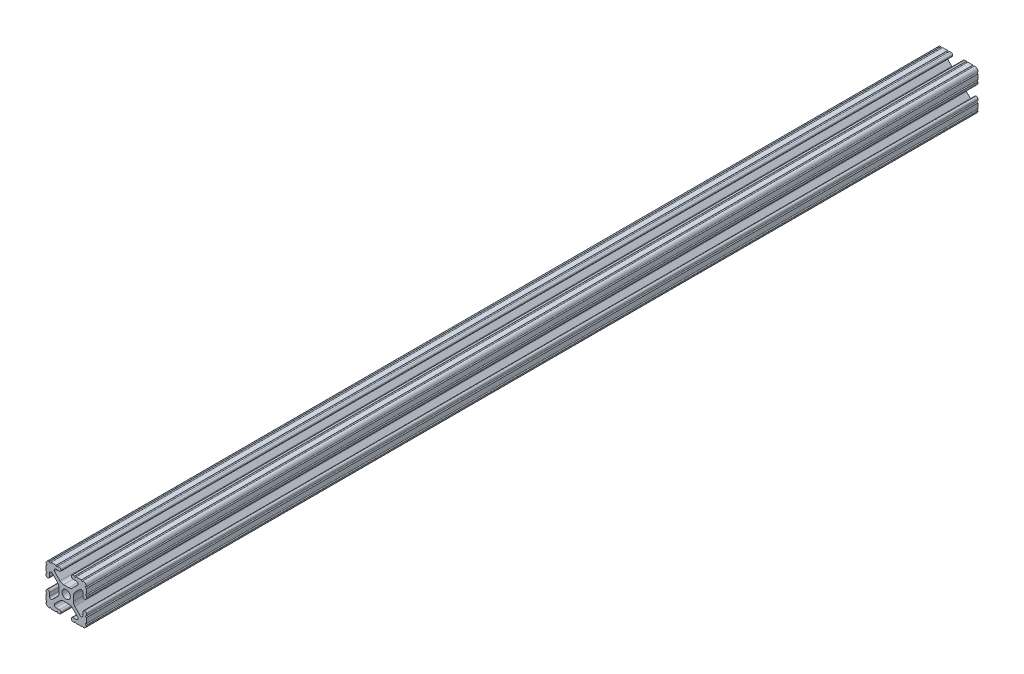
SolidWorks part; units mm, degrees
ref_plane "Front Plane" through (0, 0, 0) normal (0, 0, 1) x (1, 0, 0)
ref_plane "Top Plane" through (0, 0, 0) normal (0, 1, 0) x (1, 0, 0)
ref_plane "Right Plane" through (0, 0, 0) normal (1, 0, 0) x (0, 0, -1)
sketch "Sketch1" plane through (0, 0, 0) normal (0, 0, 1) x (1, 0, 0)
  line L88 (-7.1797, -8.6452) -> (-3.9523, -5.4237)
  line L89 (-1.7093, -4.4958) -> (1.7093, -4.4958)
  line L90 (3.9523, -5.4237) -> (7.1797, -8.6452)
  line L91 (6.4164, -10.4902) -> (4.2875, -10.4902)
  line L92 (3.2385, -11.5392) -> (3.2385, -11.651)
  line L93 (4.2875, -12.7) -> (5.3171, -12.7)
  line L94 (6.3331, -12.7) -> (9.5504, -12.7)
  line L95 (12.7, -9.5504) -> (12.7, -6.3331)
  line L96 (12.7, -5.3171) -> (12.7, -4.2875)
  line L97 (11.651, -3.2385) -> (11.5392, -3.2385)
  line L98 (10.4902, -4.2875) -> (10.4902, -6.4021)
  line L99 (8.7371, -7.1294) -> (5.441, -3.8408)
  line L100 (4.5085, -1.5932) -> (4.5085, 1.5932)
  line L101 (5.441, 3.8408) -> (8.7371, 7.1294)
  line L102 (10.4902, 6.4021) -> (10.4902, 4.2875)
  line L103 (11.5392, 3.2385) -> (11.651, 3.2385)
  line L104 (12.7, 4.2875) -> (12.7, 5.3171)
  line L105 (12.7, 6.3331) -> (12.7, 9.5504)
  line L106 (9.5504, 12.7) -> (6.3331, 12.7)
  line L107 (5.3171, 12.7) -> (4.2875, 12.7)
  line L108 (3.2385, 11.651) -> (3.2385, 11.5392)
  line L109 (4.2875, 10.4902) -> (6.4768, 10.4902)
  line L110 (7.207, 8.7244) -> (3.8983, 5.4232)
  line L111 (1.6558, 4.4958) -> (-1.6558, 4.4958)
  line L112 (-3.8983, 5.4232) -> (-7.207, 8.7244)
  line L113 (-6.4768, 10.4902) -> (-4.2875, 10.4902)
  line L114 (-3.2385, 11.5392) -> (-3.2385, 11.651)
  line L115 (-4.2875, 12.7) -> (-5.3171, 12.7)
  line L116 (-6.3331, 12.7) -> (-9.5504, 12.7)
  line L117 (-12.7, 9.5504) -> (-12.7, 6.3331)
  line L118 (-12.7, 5.3171) -> (-12.7, 4.2875)
  line L119 (-11.651, 3.2385) -> (-11.5392, 3.2385)
  line L120 (-10.4902, 4.2875) -> (-10.4902, 6.4021)
  line L121 (-8.7371, 7.1294) -> (-5.441, 3.8408)
  line L122 (-4.5085, 1.5932) -> (-4.5085, -1.5932)
  line L123 (-5.441, -3.8408) -> (-8.7371, -7.1294)
  line L124 (-10.4902, -6.4021) -> (-10.4902, -4.2875)
  line L125 (-11.5392, -3.2385) -> (-11.651, -3.2385)
  line L126 (-12.7, -4.2875) -> (-12.7, -5.3171)
  line L127 (-12.7, -6.3331) -> (-12.7, -9.5504)
  line L128 (-9.5504, -12.7) -> (-6.3331, -12.7)
  line L129 (-5.3171, -12.7) -> (-4.2875, -12.7)
  line L130 (-3.2385, -11.651) -> (-3.2385, -11.5392)
  line L131 (-4.2875, -10.4902) -> (-6.4164, -10.4902)
  circle A1 centre (0, 0) radius 2.6035
  arc A104 (-7.1797, -8.6452) -> (-6.4164, -10.4902) centre (-6.4164, -9.4098) ccw
  arc A105 (-1.7093, -4.4958) -> (-3.9523, -5.4237) centre (-1.7093, -7.6708) ccw
  arc A106 (3.9523, -5.4237) -> (1.7093, -4.4958) centre (1.7093, -7.6708) ccw
  arc A107 (6.4164, -10.4902) -> (7.1797, -8.6452) centre (6.4164, -9.4098) ccw
  arc A108 (4.2875, -10.4902) -> (3.2385, -11.5392) centre (4.2875, -11.5392) ccw
  arc A109 (3.2385, -11.651) -> (4.2875, -12.7) centre (4.2875, -11.651) ccw
  arc A110 (6.3331, -12.7) -> (5.3171, -12.7) centre (5.8251, -12.7) ccw
  arc A111 (10.5664, -12.6998) -> (9.5504, -12.7) centre (10.0584, -12.7) ccw
  arc A112 (10.5664, -12.6998) -> (12.6998, -10.5664) centre (10.5918, -10.5918) ccw
  arc A113 (12.7, -9.5504) -> (12.6998, -10.5664) centre (12.7, -10.0584) ccw
  arc A114 (12.7, -5.3171) -> (12.7, -6.3331) centre (12.7, -5.8251) ccw
  arc A115 (12.7, -4.2875) -> (11.651, -3.2385) centre (11.651, -4.2875) ccw
  arc A116 (11.5392, -3.2385) -> (10.4902, -4.2875) centre (11.5392, -4.2875) ccw
  arc A117 (8.7371, -7.1294) -> (10.4902, -6.4021) centre (9.4628, -6.4021) ccw
  arc A118 (4.5085, -1.5932) -> (5.441, -3.8408) centre (7.6835, -1.5932) ccw
  arc A119 (5.441, 3.8408) -> (4.5085, 1.5932) centre (7.6835, 1.5932) ccw
  arc A120 (10.4902, 6.4021) -> (8.7371, 7.1294) centre (9.4628, 6.4021) ccw
  arc A121 (10.4902, 4.2875) -> (11.5392, 3.2385) centre (11.5392, 4.2875) ccw
  arc A122 (11.651, 3.2385) -> (12.7, 4.2875) centre (11.651, 4.2875) ccw
  arc A123 (12.7, 6.3331) -> (12.7, 5.3171) centre (12.7, 5.8251) ccw
  arc A124 (12.6998, 10.5664) -> (12.7, 9.5504) centre (12.7, 10.0584) ccw
  arc A125 (12.6998, 10.5664) -> (10.5664, 12.6998) centre (10.5918, 10.5918) ccw
  arc A126 (9.5504, 12.7) -> (10.5664, 12.6998) centre (10.0584, 12.7) ccw
  arc A127 (5.3171, 12.7) -> (6.3331, 12.7) centre (5.8251, 12.7) ccw
  arc A128 (4.2875, 12.7) -> (3.2385, 11.651) centre (4.2875, 11.651) ccw
  arc A129 (3.2385, 11.5392) -> (4.2875, 10.4902) centre (4.2875, 11.5392) ccw
  arc A130 (7.207, 8.7244) -> (6.4768, 10.4902) centre (6.4768, 9.4563) ccw
  arc A131 (1.6558, 4.4958) -> (3.8983, 5.4232) centre (1.6558, 7.6708) ccw
  arc A132 (-3.8983, 5.4232) -> (-1.6558, 4.4958) centre (-1.6558, 7.6708) ccw
  arc A133 (-6.4768, 10.4902) -> (-7.207, 8.7244) centre (-6.4768, 9.4563) ccw
  arc A134 (-4.2875, 10.4902) -> (-3.2385, 11.5392) centre (-4.2875, 11.5392) ccw
  arc A135 (-3.2385, 11.651) -> (-4.2875, 12.7) centre (-4.2875, 11.651) ccw
  arc A136 (-6.3331, 12.7) -> (-5.3171, 12.7) centre (-5.8251, 12.7) ccw
  arc A137 (-10.5664, 12.6998) -> (-9.5504, 12.7) centre (-10.0584, 12.7) ccw
  arc A138 (-10.5664, 12.6998) -> (-12.6998, 10.5664) centre (-10.5918, 10.5918) ccw
  arc A139 (-12.7, 9.5504) -> (-12.6998, 10.5664) centre (-12.7, 10.0584) ccw
  arc A140 (-12.7, 5.3171) -> (-12.7, 6.3331) centre (-12.7, 5.8251) ccw
  arc A141 (-12.7, 4.2875) -> (-11.651, 3.2385) centre (-11.651, 4.2875) ccw
  arc A142 (-11.5392, 3.2385) -> (-10.4902, 4.2875) centre (-11.5392, 4.2875) ccw
  arc A143 (-8.7371, 7.1294) -> (-10.4902, 6.4021) centre (-9.4628, 6.4021) ccw
  arc A144 (-4.5085, 1.5932) -> (-5.441, 3.8408) centre (-7.6835, 1.5932) ccw
  arc A145 (-5.441, -3.8408) -> (-4.5085, -1.5932) centre (-7.6835, -1.5932) ccw
  arc A146 (-10.4902, -6.4021) -> (-8.7371, -7.1294) centre (-9.4628, -6.4021) ccw
  arc A147 (-10.4902, -4.2875) -> (-11.5392, -3.2385) centre (-11.5392, -4.2875) ccw
  arc A148 (-11.651, -3.2385) -> (-12.7, -4.2875) centre (-11.651, -4.2875) ccw
  arc A149 (-12.7, -6.3331) -> (-12.7, -5.3171) centre (-12.7, -5.8251) ccw
  arc A150 (-12.6998, -10.5664) -> (-12.7, -9.5504) centre (-12.7, -10.0584) ccw
  arc A151 (-12.6998, -10.5664) -> (-10.5664, -12.6998) centre (-10.5918, -10.5918) ccw
  arc A152 (-9.5504, -12.7) -> (-10.5664, -12.6998) centre (-10.0584, -12.7) ccw
  arc A153 (-5.3171, -12.7) -> (-6.3331, -12.7) centre (-5.8251, -12.7) ccw
  arc A154 (-4.2875, -12.7) -> (-3.2385, -11.651) centre (-4.2875, -11.651) ccw
  arc A155 (-3.2385, -11.5392) -> (-4.2875, -10.4902) centre (-4.2875, -11.5392) ccw
extrude "Boss-Extrude1" add sketch "Sketch1" along normal mid plane 609.6
sketch "Sketch2" plane through (0, 0, 304.8) normal (0, 0, 1) x (1, 0, 0)
  line L1 (-15.7211, 17.4905) -> (17.9177, 17.4905)
  line L2 (-15.7211, 17.4905) -> (-15.7211, -19.7221)
  line L3 (-15.7211, -19.7221) -> (17.9177, -19.7221)
  line L4 (17.9177, 17.4905) -> (17.9177, -19.7221)
extrude "Cut-Extrude1" cut sketch "Sketch2" against normal blind 48.26
